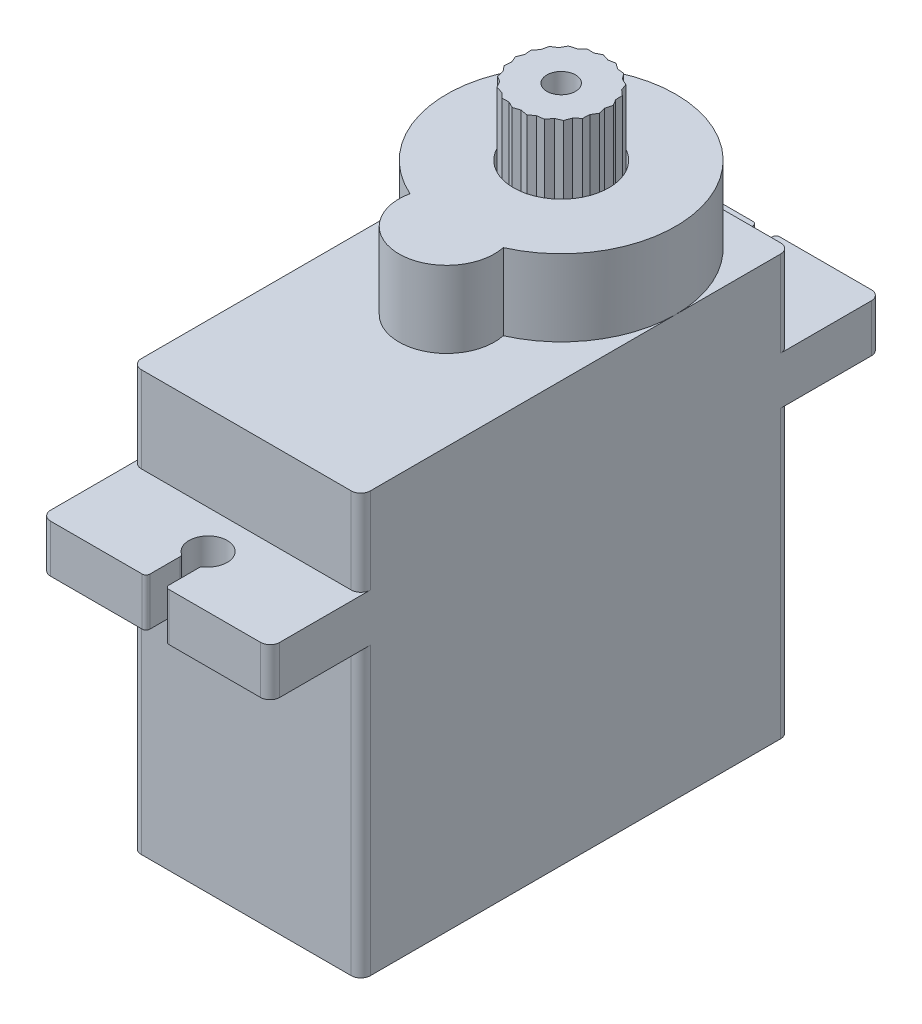
SolidWorks part; units mm, degrees
ref_plane "Ön Düzlem" through (0, 0, 0) normal (0, 0, 1) x (1, 0, 0)
ref_plane "Üst Düzlem" through (0, 0, 0) normal (0, 1, 0) x (1, 0, 0)
ref_plane "Sağ Düzlem" through (0, 0, 0) normal (1, 0, 0) x (0, 0, -1)
sketch "Çizim1" plane through (0, 0, 0) normal (0, 1, 0) x (1, 0, 0)
  line L1 (-5.5, 11.25) -> (5.5, 11.25)
  line L2 (-6, 10.75) -> (-6, -10.75)
  line L3 (-5.5, -11.25) -> (5.5, -11.25)
  line L4 (6, 10.75) -> (6, -10.75)
  line L5 (-6, 11.25) -> (6, -11.25) construction
  line L6 (-6, -11.25) -> (6, 11.25) construction
  arc A0 (5.5, -11.25) -> (6, -10.75) centre (5.5, -10.75) ccw
  arc A1 (-6, -10.75) -> (-5.5, -11.25) centre (-5.5, -10.75) ccw
  arc A2 (5.5, 11.25) -> (6, 10.75) centre (5.5, 10.75) cw
  arc A3 (-5.5, 11.25) -> (-6, 10.75) centre (-5.5, 10.75) ccw
  point P0 (0, 0)
  dimension "D3" = 0.5
  dimension "D1" = 12
  dimension "D2" = 22.5
extrude "Yükseklik-Ekstrüzyon1" add sketch "Çizim1" along normal blind 1
sketch "Çizim2" plane through (0, 1, 0) normal (0, 1, 0) x (1, 0, 0)
  line L0 (-5, 9.25) -> (-5, -9.25)
  line L1 (-5.5, 11.25) -> (5.5, 11.25)
  line L2 (-6, 10.75) -> (-6, -10.75)
  line L3 (-5.5, -11.25) -> (5.5, -11.25)
  line L4 (6, 10.75) -> (6, -10.75)
  line L5 (-6, 11.25) -> (-5.8961, 11.0552) construction
  line L6 (-6, -11.25) -> (-5.8961, -11.0552) construction
  line L7 (-4, -10.25) -> (4, -10.25)
  line L8 (5, 9.25) -> (5, -9.25)
  line L9 (-4, 10.25) -> (4, 10.25)
  line L10 (-6, -11.25) -> (6, -11.25) construction
  line L11 (6, 11.25) -> (6, -11.25) construction
  line L12 (-6, 11.25) -> (-6, -11.25) construction
  line L13 (-6, 11.25) -> (6, 11.25) construction
  line L14 (-5, 10.25) -> (5, 10.25) construction
  line L15 (-5, 10.25) -> (-5, -10.25) construction
  line L16 (-4.9345, 9.2521) -> (4.9345, -9.2521) construction
  line L17 (5, 10.25) -> (5, -10.25) construction
  line L18 (5.8961, 11.0552) -> (6, 11.25) construction
  line L19 (-5, -10.25) -> (5, -10.25) construction
  line L20 (5.8961, -11.0552) -> (6, -11.25) construction
  line L21 (-4.9345, -9.2521) -> (4.9345, 9.2521) construction
  arc A0 (5.5, -11.25) -> (6, -10.75) centre (5.5, -10.75) ccw
  arc A1 (-6, -10.75) -> (-5.5, -11.25) centre (-5.5, -10.75) ccw
  arc A2 (5.5, 11.25) -> (6, 10.75) centre (5.5, 10.75) cw
  arc A3 (-5.5, 11.25) -> (-6, 10.75) centre (-5.5, 10.75) ccw
  arc A5 (4, 10.25) -> (5, 9.25) centre (5, 10.25) ccw
  arc A7 (-4, -10.25) -> (-5, -9.25) centre (-5, -10.25) ccw
  arc A8 (-5, 9.25) -> (-4, 10.25) centre (-5, 10.25) ccw
  arc A9 (5, -9.25) -> (4, -10.25) centre (5, -10.25) ccw
  point P0 (0, 0)
  dimension "D2" = 0.5
  dimension "D1" = 1
extrude "Yükseklik-Ekstrüzyon2" add sketch "Çizim2" along normal blind 5
sketch "Çizim3" plane through (0, 6, 0) normal (0, 1, 0) x (1, 0, 0)
  line L0 (0, -10.25) -> (0, -11.25) construction
  line L1 (-4, -10.25) -> (4, -10.25) construction
  line L2 (-5.5, -11.25) -> (5.5, -11.25) construction
  line L3 (0, -11.25) -> (0, -10.75) construction
  line L4 (0, -10.75) -> (2.4368, -10.75) construction
  line L6 (-2, -10.25) -> (2, -10.25)
  line L7 (-2, -10.25) -> (-2, -11.25)
  line L8 (-2, -11.25) -> (2, -11.25)
  line L9 (2, -10.25) -> (2, -11.25)
  line L10 (-2, -10.25) -> (2, -11.25) construction
  line L11 (-2, -11.25) -> (2, -10.25) construction
  dimension "D1" = 4
extrude "Kes-Ekstrüzyon1" cut sketch "Çizim3" against normal blind 1
fillet "Radyus1" radius 0.1 2 edges at (2, 5, 10.75) (-2, 5, 10.75)
sketch "Çizim4" plane through (0, 6, 0) normal (0, 1, 0) x (1, 0, 0)
  line L0 (-4, 10.25) -> (4, 10.25)
  line L1 (-5.5, 11.25) -> (5.5, 11.25)
  line L2 (-6, 10.75) -> (-6, -10.75)
  line L3 (-5.5, -11.25) -> (5.5, -11.25)
  line L4 (6, 10.75) -> (6, -10.75)
  line L5 (-6, 11.25) -> (-5.8961, 11.0552) construction
  line L6 (-6, -11.25) -> (-5.8961, -11.0552) construction
  line L7 (-4, 10.25) -> (4, 10.25)
  line L8 (5, 9.25) -> (5, -9.25)
  line L9 (5, -9.25) -> (5, 9.25)
  line L10 (-4, 10.25) -> (4, 10.25)
  line L11 (5, 9.25) -> (5, -9.25)
  line L12 (-4, -10.25) -> (4, -10.25)
  line L13 (-5, 9.25) -> (-5, -9.25)
  line L14 (-4.9345, 9.2521) -> (4.9345, -9.2521) construction
  line L15 (-5, 10.25) -> (-5, -10.25) construction
  line L16 (-5, 10.25) -> (5, 10.25) construction
  line L17 (5, 10.25) -> (5, -10.25) construction
  line L18 (5.8961, 11.0552) -> (6, 11.25) construction
  line L19 (5.8961, -11.0552) -> (6, -11.25) construction
  line L20 (-5, -10.25) -> (5, -10.25) construction
  line L21 (-4.9345, -9.2521) -> (4.9345, 9.2521) construction
  arc A0 (5.5, -11.25) -> (6, -10.75) centre (5.5, -10.75) ccw
  arc A1 (-6, -10.75) -> (-5.5, -11.25) centre (-5.5, -10.75) ccw
  arc A2 (5.5, 11.25) -> (6, 10.75) centre (5.5, 10.75) cw
  arc A3 (-5.5, 11.25) -> (-6, 10.75) centre (-5.5, 10.75) ccw
  arc A4 (-5, 9.25) -> (-4, 10.25) centre (-5, 10.25) ccw
  arc A5 (4, 10.25) -> (5, 9.25) centre (5, 10.25) ccw
  arc A6 (-4, -10.25) -> (-5, -9.25) centre (-5, -10.25) ccw
  arc A7 (5, -9.25) -> (4, -10.25) centre (5, -10.25) ccw
  arc A8 (5, 10.25) -> (5, 10.25) centre (5, 10.25) cw
  arc A9 (5, -10.25) -> (5, -10.25) centre (5, -10.25) ccw
  arc A10 (-5, -10.25) -> (-5, -10.25) centre (-5, -10.25) ccw
  arc A11 (-5, 10.25) -> (-5, 10.25) centre (-5, 10.25) ccw
  point P0 (0, 0)
  line M12 (4, -10.25) -> (2, -10.25)
  line M14 (2, -11.25) -> (5.5, -11.25)
  arc M15 (5.5, -11.25) -> (6, -10.75) centre (5.5, -10.75) ccw
  line M16 (6, -10.75) -> (6, 10.75)
  arc M17 (6, 10.75) -> (5.5, 11.25) centre (5.5, 10.75) ccw
  line M18 (5.5, 11.25) -> (-5.5, 11.25)
  arc M19 (-5.5, 11.25) -> (-6, 10.75) centre (-5.5, 10.75) ccw
  line M20 (-6, 10.75) -> (-6, -10.75)
  arc M21 (-6, -10.75) -> (-5.5, -11.25) centre (-5.5, -10.75) ccw
  line M22 (-5.5, -11.25) -> (-2, -11.25)
  line M24 (-2, -10.25) -> (-4, -10.25)
  arc M25 (-4, -10.25) -> (-5, -9.25) centre (-5, -10.25) ccw
  line M26 (-5, -9.25) -> (-5, 9.25)
  arc M27 (-5, 9.25) -> (-4, 10.25) centre (-5, 10.25) ccw
  line M28 (-4, 10.25) -> (4, 10.25)
  arc M29 (4, 10.25) -> (5, 9.25) centre (5, 10.25) ccw
  line M30 (5, 9.25) -> (5, -9.25)
  arc M31 (5, -9.25) -> (4, -10.25) centre (5, -10.25) ccw
  dimension "D1" = 0.5
  dimension "D2" = 1
extrude "Yükseklik-Ekstrüzyon4" add sketch "Çizim4" along normal blind 9 contours M31 M12 M14 M15 M16 M17 M18 M19 M20 M21 M22 M24 M25 M26 M27 M28 M29 M30 | L12 L3 region at (0, 6, -10.995)
sketch "Çizim6" plane through (0, 15, 0) normal (0, 1, 0) x (1, 0, 0)
  line L0 (0, -10.25) -> (0, -12.25) construction
  line L1 (-5.5, 16) -> (-0.7, 16)
  line L2 (-6, 15.5) -> (-6, -15.5)
  line L3 (-5.5, -16) -> (-0.7, -16)
  line L4 (6, 15.5) -> (6, -15.5)
  line L5 (-6, 16) -> (6, -16) construction
  line L6 (-3.8437, -10.25) -> (6, 16) construction
  line L7 (-4, 10.25) -> (4, 10.25)
  line L8 (-5, 9.25) -> (-5, -9.25)
  line L9 (-4, -10.25) -> (4, -10.25)
  line L10 (5, 9.25) -> (5, -9.25)
  line L11 (-4.5616, 9.3512) -> (4.5616, -9.3512) construction
  line L12 (-4.5616, -9.3512) -> (4.5616, 9.3512) construction
  line L13 (0, -12.25) -> (0, -11.25) construction
  line L14 (-5.5, -11.25) -> (5.5, -11.25) construction
  line L15 (0, -11.25) -> (8.7476, -11.25) construction
  line L16 (0, -12.25) -> (8.7476, -12.25) construction
  line L17 (0.7, -16) -> (5.5, -16)
  line L18 (-0.5, -14.2247) -> (-0.5, -15.8)
  line L19 (0.5, -14.2247) -> (0.5, -15.8)
  line L20 (0, 0) -> (5, 0) construction
  line L21 (0.5, 14.2247) -> (0.5, 15.8)
  line L22 (-0.5, 14.2247) -> (-0.5, 15.8)
  line L23 (0.7, 16) -> (5.5, 16)
  arc A0 (-5, 9.25) -> (-4, 10.25) centre (-5, 10.25) ccw
  arc A1 (4, 10.25) -> (5, 9.25) centre (5, 10.25) ccw
  arc A2 (5, -9.25) -> (4, -10.25) centre (5, -10.25) ccw
  arc A3 (-4, -10.25) -> (-5, -9.25) centre (-5, -10.25) ccw
  arc A4 (5.5, -16) -> (6, -15.5) centre (5.5, -15.5) ccw
  arc A5 (-6, -15.5) -> (-5.5, -16) centre (-5.5, -15.5) ccw
  arc A6 (5.5, 16) -> (6, 15.5) centre (5.5, 15.5) cw
  arc A7 (-5.5, 16) -> (-6, 15.5) centre (-5.5, 15.5) ccw
  arc A9 (0.5833, -14.0622) -> (-0.5833, -14.0622) centre (0, -13.25) ccw
  arc A10 (0.5, -14.2247) -> (0.5833, -14.0622) centre (0.7, -14.2247) cw
  arc A11 (-0.5, -14.2247) -> (-0.5833, -14.0622) centre (-0.7, -14.2247) ccw
  arc A12 (0.5, -15.8) -> (0.7, -16) centre (0.7, -15.8) ccw
  arc A13 (-0.5, -15.8) -> (-0.7, -16) centre (-0.7, -15.8) cw
  arc A14 (0.5, 15.8) -> (0.7, 16) centre (0.7, 15.8) cw
  arc A15 (-0.5, 15.8) -> (-0.7, 16) centre (-0.7, 15.8) ccw
  arc A16 (0.5, 14.2247) -> (0.5833, 14.0622) centre (0.7, 14.2247) ccw
  arc A17 (-0.5, 14.2247) -> (-0.5833, 14.0622) centre (-0.7, 14.2247) cw
  arc A18 (0.5833, 14.0622) -> (-0.5833, 14.0622) centre (0, 13.25) cw
  point P0 (0, 0)
  point P6 (0, 0)
  point P54 (0.5, -16)
  dimension "D2" = 0.5
  dimension "D4" = 2
  dimension "D5" = 0.2
  dimension "D1" = 32
  dimension "D3" = 1
extrude "Yükseklik-Ekstrüzyon5" add sketch "Çizim6" along normal blind 2.5
sketch "Çizim7" plane through (0, 17.5, 0) normal (0, 1, 0) x (1, 0, 0)
  line L0 (6, -15.5) -> (6, 15.5) construction
  line L1 (-5.5, 11.25) -> (5.5, 11.25)
  line L2 (-6, 10.75) -> (-6, -10.75)
  line L3 (-5.5, -11.25) -> (5.5, -11.25)
  line L4 (6, 10.75) -> (6, -10.75)
  line L5 (-6, 11.25) -> (-5.8961, 11.0552) construction
  line L6 (-6, -11.25) -> (-5.8961, -11.0552) construction
  line L7 (-5, 9.25) -> (-5, -9.25)
  line L8 (-4, 10.25) -> (4, 10.25)
  line L9 (5, 9.25) -> (5, -9.25)
  line L10 (4, -10.25) -> (-4, -10.25)
  line L12 (-4.9345, 9.2521) -> (4.9345, -9.2521) construction
  line L13 (5.8961, 11.0552) -> (6, 11.25) construction
  line L14 (5.8961, -11.0552) -> (6, -11.25) construction
  line L15 (-5, -9.25) -> (-5, 9.25)
  line L16 (-4.9345, -9.2521) -> (4.9345, 9.2521) construction
  line L17 (-5, 9.25) -> (-5, -9.25)
  arc A0 (-6, -10.75) -> (-5.5, -11.25) centre (-5.5, -10.75) ccw
  arc A1 (5.5, -11.25) -> (6, -10.75) centre (5.5, -10.75) ccw
  arc A2 (5.5, 11.25) -> (6, 10.75) centre (5.5, 10.75) cw
  arc A3 (-5.5, 11.25) -> (-6, 10.75) centre (-5.5, 10.75) ccw
  arc A4 (-5, 9.25) -> (-4, 10.25) centre (-5, 10.25) ccw
  arc A5 (4, 10.25) -> (5, 9.25) centre (5, 10.25) ccw
  arc A6 (5, -9.25) -> (4, -10.25) centre (5, -10.25) ccw
  arc A8 (-4, -10.25) -> (-5, -9.25) centre (-5, -10.25) ccw
  point P0 (0, 0)
  line M16 (6, -15.5) -> (6, 15.5)
  line M28 (-6, 15.5) -> (-6, -15.5)
  line M39 (-5, -9.25) -> (-5, 9.25)
  arc M40 (-5, 9.25) -> (-4, 10.25) centre (-5, 10.25) ccw
  line M41 (-4, 10.25) -> (4, 10.25)
  arc M42 (4, 10.25) -> (5, 9.25) centre (5, 10.25) ccw
  line M43 (5, 9.25) -> (5, -9.25)
  arc M44 (5, -9.25) -> (4, -10.25) centre (5, -10.25) ccw
  line M45 (4, -10.25) -> (-4, -10.25)
  arc M46 (-4, -10.25) -> (-5, -9.25) centre (-5, -10.25) ccw
  dimension "D2" = 0.5
  dimension "D1" = 22.5
extrude "Yükseklik-Ekstrüzyon6" add sketch "Çizim7" along normal blind 3.5 contours L1 A3 A0 L3 A1 A2 M28 M16 M46 M39 M40 M41 M42 M43 M44 M45 region at (0, 17.5, -10.995)
sketch "Çizim8" plane through (0, 21, 0) normal (0, 1, 0) x (1, 0, 0)
  line L0 (6, -15.5) -> (6, -10.75) construction
  line L1 (-5.5, 11.25) -> (5.5, 11.25)
  line L2 (-6, 10.75) -> (-6, -10.75)
  line L3 (-5.5, -11.25) -> (5.5, -11.25)
  line L4 (6, 10.75) -> (6, -10.75)
  line L5 (-6, 11.25) -> (6, -11.25) construction
  line L6 (-6, -11.25) -> (6, 11.25) construction
  arc A0 (-6, -10.75) -> (-5.5, -11.25) centre (-5.5, -10.75) ccw
  arc A1 (5.5, -11.25) -> (6, -10.75) centre (5.5, -10.75) ccw
  arc A2 (5.5, 11.25) -> (6, 10.75) centre (5.5, 10.75) cw
  arc A3 (-5.5, 11.25) -> (-6, 10.75) centre (-5.5, 10.75) ccw
  point P0 (0, 0)
  dimension "D1" = 0.5
extrude "Yükseklik-Ekstrüzyon7" add sketch "Çizim8" along normal blind 1
sketch "Çizim9" plane through (0, 22, 0) normal (0, 1, 0) x (1, 0, 0)
  line L0 (-6, 5.25) -> (6, 5.25) construction
  line L1 (-6, 10.75) -> (-6, -10.75) construction
  line L2 (6, -10.75) -> (6, 10.75) construction
  line L3 (5.5, 11.25) -> (-5.5, 11.25) construction
  line L4 (0, 5.25) -> (0, -0.75) construction
  arc A0 (2.4451, -0.2292) -> (-2.4451, -0.2292) centre (0, 5.25) ccw
  arc A1 (-2.4451, -0.2292) -> (2.4451, -0.2292) centre (0, -0.75) ccw
  arc A2 (1.0153, 0.3542) -> (-1.0153, 0.3542) centre (0, 5.25) ccw
  arc A3 (-1.0153, 0.3542) -> (1.0153, 0.3542) centre (0, -0.75) ccw
  dimension "D2" = 5
  dimension "D1" = 6
  dimension "D3" = 1
extrude "Kes-Ekstrüzyon2" cut sketch "Çizim9" against normal blind 1 contours A2 A3
extrude "Yükseklik-Ekstrüzyon8" add sketch "Çizim9<3>" along normal blind 3
sketch "Çizim9<3>" plane through (0, 22, 0) normal (0, 1, 0) x (1, 0, 0) same geometry as "Çizim9"
fillet "Radyus2" radius 0.5 2 edges at (1.0153, 23, -0.3542) (-1.0153, 23, -0.3542)
sketch "Çizim10" plane through (0, 25, 0) normal (0, 1, 0) x (1, 0, 0)
  arc A0 (2.4451, -0.2292) -> (-2.4451, -0.2292) centre (0, 5.25) ccw
  arc A1 (-2.4451, -0.2292) -> (2.4451, -0.2292) centre (0, -0.75) ccw
extrude "Yükseklik-Ekstrüzyon9" add sketch "Çizim10" along normal blind 1
sketch "Çizim11" plane through (0, 26, 0) normal (0, 1, 0) x (1, 0, 0)
  circle A0 centre (0, 5.25) radius 2.5
  dimension "D1" = 5
extrude "Kes-Ekstrüzyon3" cut sketch "Çizim11" against normal blind 10
sketch "Çizim15" plane through (0, 26, 0) normal (0, 1, 0) x (1, 0, 0)
  circle A0 centre (0, -0.75) radius 0.25
  dimension "D1" = 0.5
extrude "Yükseklik-Ekstrüzyon12" add sketch "Çizim15" against normal blind 11
ref_plane "Düzlem3" through (0, 30, 0) normal (0, 1, 0) x (1, 0, 0)
sketch "Çizim19" plane through (0, 30, 0) normal (0, 1, 0) x (1, 0, 0)
  circle A0 centre (0, 5.25) radius 2.4
  dimension "D1" = 4.8
extrude "Yükseklik-Ekstrüzyon17" add sketch "Çizim19" against normal blind 5 separate body
sketch "Çizim20" plane through (0, 25, 0) normal (0, -1, 0) x (1, 0, 0)
  circle A0 centre (0, -5.25) radius 4.75
  dimension "D1" = 9.5
extrude "Yükseklik-Ekstrüzyon18" add sketch "Çizim20" along normal blind 3
sketch "Çizim21" plane through (0, 30, 0) normal (0, 1, 0) x (1, 0, 0)
  circle A0 centre (0, 5.25) radius 0.75
  dimension "D1" = 1.5
extrude "Kes-Ekstrüzyon5" cut sketch "Çizim21" against normal blind 10
ref_plane "Düzlem4" through (0, 25.5, 0) normal (0, 1, 0) x (1, 0, 0)
sketch "Çizim22" plane through (0, 25.5, 0) normal (0, 1, 0) x (1, 0, 0)
  line L0 (0, 11.25) -> (0, -3.25) construction
  arc A0 (2.4451, -0.2292) -> (-2.4451, -0.2292) centre (0, 5.25) ccw construction
  arc A1 (-2.4451, -0.2292) -> (2.4451, -0.2292) centre (0, -0.75) ccw construction
  circle A2 centre (0, -0.75) radius 0.5
  dimension "D1" = 1
extrude "Yükseklik-Ekstrüzyon19" add sketch "Çizim22" against normal blind 5
sketch "Çizim23" plane through (0, 20.5, 0) normal (0, -1, 0) x (1, 0, 0)
  circle A0 centre (0, 0.75) radius 4
  dimension "D1" = 8
extrude "Yükseklik-Ekstrüzyon20" add sketch "Çizim23" along normal blind 2
sketch "Çizim24" plane through (0, 22, 0) normal (0, -1, 0) x (1, 0, 0)
  circle A0 centre (0, -5.25) radius 0.75
extrude "Yükseklik-Ekstrüzyon21" add sketch "Çizim24" along normal blind 7 separate body
ref_plane "Düzlem5" through (0, 19, 0) normal (0, -1, 0) x (-1, 0, 0)
sketch "Çizim25" plane through (0, 19, 0) normal (0, -1, 0) x (-1, 0, 0)
  circle A0 centre (0, 5.25) radius 3.5
  dimension "D1" = 7
extrude "Yükseklik-Ekstrüzyon22" add sketch "Çizim25" along normal blind 1
ref_plane "Düzlem6" through (0, 17.5, 0) normal (0, -1, 0) x (-1, 0, 0)
sketch "Çizim26" plane through (0, 17.5, 0) normal (0, -1, 0) x (-1, 0, 0)
  circle A0 centre (0, -0.75) radius 4.5
  dimension "D1" = 9
extrude "Yükseklik-Ekstrüzyon23" add sketch "Çizim26" along normal blind 1
sketch "Çizim32" plane through (0, 0, 10.25) normal (0, 0, -1) x (-1, 0, 0)
  line L1 (2, 6) -> (-2, 6)
  line L2 (2, 6) -> (2, 5.1)
  line L3 (1.9, 5) -> (-1.9, 5)
  line L4 (-2, 6) -> (-2, 5.1)
  arc A0 (-1.9, 5) -> (-2, 5.1) centre (-1.9, 5.1) cw
  arc A1 (2, 5.1) -> (1.9, 5) centre (1.9, 5.1) cw
  point P7 (-2, 5)
  dimension "D3" = 0.1
  dimension "D1" = 1
  dimension "D2" = 4
extrude "Kes-Ekstrüzyon7" cut sketch "Çizim32" along normal blind 30
sketch "Çizim33" plane through (0, 0, 11.25) normal (0, 0, 1) x (1, 0, 0)
  line L1 (-2, 6) -> (2, 6)
  line L2 (-2, 6) -> (-2, 5.1)
  line L3 (-1.9, 5) -> (1.9, 5)
  line L4 (2, 6) -> (2, 5.1)
  arc A0 (1.9, 5) -> (2, 5.1) centre (1.9, 5.1) ccw
  arc A1 (-2, 5.1) -> (-1.9, 5) centre (-1.9, 5.1) ccw
  point P7 (2, 5)
  point P10 (-2, 5)
  dimension "D3" = 0.1
  dimension "D1" = 1
  dimension "D2" = 4
extrude "Yükseklik-Ekstrüzyon33" add sketch "Çizim33" against normal blind 1
sketch "Çizim34" plane through (0, 1, 0) normal (0, 1, 0) x (1, 0, 0)
  line L0 (-5, -6.25) -> (5, -6.25) construction
  line L1 (-5, 9.25) -> (-5, -9.25) construction
  line L2 (5, -9.25) -> (5, 9.25) construction
  line L3 (-4, -10.25) -> (4, -10.25) construction
  line L5 (-3, -3.25) -> (3, -3.25)
  line L6 (-4, -4.25) -> (-4, -8.25)
  line L7 (-3, -9.25) -> (3, -9.25)
  line L8 (4, -4.25) -> (4, -8.25)
  line L9 (-4, -3.25) -> (4, -9.25) construction
  line L10 (-4, -9.25) -> (4, -3.25) construction
  arc A0 (3, -9.25) -> (4, -8.25) centre (3, -8.25) ccw
  arc A1 (-4, -8.25) -> (-3, -9.25) centre (-3, -8.25) ccw
  arc A2 (3, -3.25) -> (4, -4.25) centre (3, -4.25) cw
  arc A3 (-3, -3.25) -> (-4, -4.25) centre (-3, -4.25) ccw
  point P8 (0, -6.25)
  dimension "D4" = 1
  dimension "D1" = 4
  dimension "D2" = 6
  dimension "D3" = 8
extrude "Yükseklik-Ekstrüzyon34" add sketch "Çizim34" along normal blind 14
ref_plane "Düzlem8" through (0, 1, 0) normal (0, -1, 0) x (-1, 0, 0)
sketch "Çizim37" plane through (0, 1, 0) normal (0, -1, 0) x (-1, 0, 0)
  line L0 (4, -6.25) -> (-4, -6.25) construction
  line L1 (4, -4.25) -> (4, -8.25) construction
  line L2 (-4, -8.25) -> (-4, -4.25) construction
  line L4 (4, -9.25) -> (-4, -9.25)
  line L5 (4, -9.25) -> (4, -3.25)
  line L6 (4, -3.25) -> (-4, -3.25)
  line L7 (-4, -9.25) -> (-4, -3.25)
  line L8 (4, -9.25) -> (-4, -3.25) construction
  line L9 (4, -3.25) -> (-4, -9.25) construction
  point P6 (0, -6.25)
  dimension "D1" = 6
  dimension "D2" = 8
extrude "Yükseklik-Ekstrüzyon36" add sketch "Çizim37" against normal blind 1
ref_plane "Düzlem9" through (0, 0, -10.75) normal (0, 0, -1) x (-1, 0, 0)
sketch "Çizim39" plane through (0, 0, -10.75) normal (0, 0, -1) x (-1, 0, 0)
  line L0 (0, 0) -> (0, 6.0146) construction
  line L1 (-5.5, 0) -> (5.5, 0) construction
  line L2 (-2, 6.0146) -> (2, 6.0146)
  line L4 (-2, 6.0146) -> (-2, 5.0146)
  line L5 (-2, 5.0146) -> (2, 5.0146)
  line L6 (2, 6.0146) -> (2, 5.0146)
  line L7 (0, 6.0146) -> (2, 5.0146) construction
  line L8 (-2, 5.0146) -> (0, 6.0146) construction
extrude "Yükseklik-Ekstrüzyon37" add sketch "Çizim39" along normal blind 0.1
sketch "Çizim40" plane through (0, 0, -10.85) normal (0, 0, -1) x (-1, 0, 0)
  line L0 (-2, 5.55) -> (2, 5.55) construction
  line L1 (-2, 6) -> (-2, 5.1) construction
  line L2 (2, 5.1) -> (2, 6) construction
  circle A0 centre (0, 5.55) radius 0.4
  circle A1 centre (1, 5.55) radius 0.4
  circle A2 centre (-1, 5.55) radius 0.4
  dimension "D1" = 0.8
  dimension "D2" = 1
  dimension "D3" = 1
extrude "Yükseklik-Ekstrüzyon38" add sketch "Çizim40" along normal blind 2
sketch "Çizim41" plane through (0, 30, 0) normal (0, 1, 0) x (1, 0, 0)
  line L0 (0, 5.25) -> (-2.4, 5.25) construction
  circle A0 centre (0, 5.25) radius 2.4
  circle A1 centre (-2.4, 5.25) radius 0.15
  circle A2 centre (-2.3614, 5.6785) radius 0.15
  circle A3 centre (-2.247, 6.0933) radius 0.15
  circle A4 centre (-2.0603, 6.481) radius 0.15
  circle A5 centre (-1.8074, 6.8291) radius 0.15
  circle A6 centre (-1.4964, 7.1264) radius 0.15
  circle A7 centre (-1.1373, 7.3634) radius 0.15
  circle A8 centre (-0.7416, 7.5325) radius 0.15
  circle A9 centre (-0.3222, 7.6283) radius 0.15
  circle A10 centre (0.1077, 7.6476) radius 0.15
  circle A11 centre (0.5341, 7.5898) radius 0.15
  circle A12 centre (0.9433, 7.4569) radius 0.15
  circle A13 centre (1.3222, 7.253) radius 0.15
  circle A14 centre (1.6586, 6.9847) radius 0.15
  circle A15 centre (1.9416, 6.6607) radius 0.15
  circle A16 centre (2.1623, 6.2913) radius 0.15
  circle A17 centre (2.3135, 5.8885) radius 0.15
  circle A18 centre (2.3903, 5.4651) radius 0.15
  circle A19 centre (2.3903, 5.0349) radius 0.15
  circle A20 centre (2.3135, 4.6115) radius 0.15
  circle A21 centre (2.1623, 4.2087) radius 0.15
  circle A22 centre (1.9416, 3.8393) radius 0.15
  circle A23 centre (1.6586, 3.5153) radius 0.15
  circle A24 centre (1.3222, 3.247) radius 0.15
  circle A25 centre (0.9433, 3.0431) radius 0.15
  circle A26 centre (0.5341, 2.9102) radius 0.15
  circle A27 centre (0.1077, 2.8524) radius 0.15
  circle A28 centre (-0.3222, 2.8717) radius 0.15
  circle A29 centre (-0.7416, 2.9675) radius 0.15
  circle A30 centre (-1.1373, 3.1366) radius 0.15
  circle A31 centre (-1.4964, 3.3736) radius 0.15
  circle A32 centre (-1.8074, 3.6709) radius 0.15
  circle A33 centre (-2.0603, 4.019) radius 0.15
  circle A34 centre (-2.247, 4.4067) radius 0.15
  circle A35 centre (-2.3614, 4.8215) radius 0.15
  circle A36 centre (0, 5.25) radius 2.4 construction
  point P75 (0, 5.25)
  circle M3 centre (0, 5.25) radius 2.4
  dimension "D1" = 0.3
  dimension "D2" = 35
extrude "Kes-Ekstrüzyon8" [suppressed] cut sketch "Çizim41" against normal blind 5 contours A1 A0 M3 | A1 L0 A0 | L0 A1 M3 | A3 | A2 | A35 | A34 | A33 | A32 | A31 | A30 | A29 | A28 | A27 | A26 | A25 | A24 | A23 | A22 | A21 | A20 | A19 | A18 | A17 | A16 | A15 | A14 | A13 | A12 | A11 | A10 | A9 | A8 | A7 | A6 | A5 | A4
sketch "Sketch1" plane through (0, 30, 0) normal (0, 1, 0) x (1, 0, 0)
  line L0 (2.3721, 5.615) -> (2.28, 5.25)
  line L1 (2.28, 5.25) -> (2.3721, 4.885)
  line L2 (2.3721, 5.615) -> (2.4721, 5.615)
  line L3 (2.4721, 5.615) -> (2.4721, 4.885)
  line L4 (2.4721, 4.885) -> (2.3721, 4.885)
  circle A0 centre (0, 5.25) radius 2.4 construction
  circle A1 centre (0, 5.25) radius 2.4 construction
  circle A2 centre (0, 5.25) radius 2.4 construction
  dimension "D1" = 2.28
  dimension "D2" = 0.73
  dimension "D3" = 0.1
extrude "Cut-Extrude1" cut sketch "Sketch1" against normal up to surface (5 mm away) up to face at (0, 25, -2.85)
pattern_circular "CirPattern1" count 21 over 360 about axis through (0, 30, -5.25) along (0, 1, 0) of "Cut-Extrude1"
sketch "Sketch2" plane through (0, 30, 0) normal (0, 1, 0) x (1, 0, 0)
  line L0 (6, 10.75) -> (6, 15.5) construction
  line L1 (-6, -0.75) -> (6, -0.75)
  line L2 (-6, -0.75) -> (-6, 11.25)
  line L3 (-6, 11.25) -> (6, 11.25)
  line L4 (6, -0.75) -> (6, 11.25)
  line L5 (-6, -0.75) -> (6, 11.25) construction
  line L6 (-6, 11.25) -> (6, -0.75) construction
  point P0 (0, 5.25)
extrude "Cut-Extrude2" cut sketch "Sketch2" against normal blind 0.5
